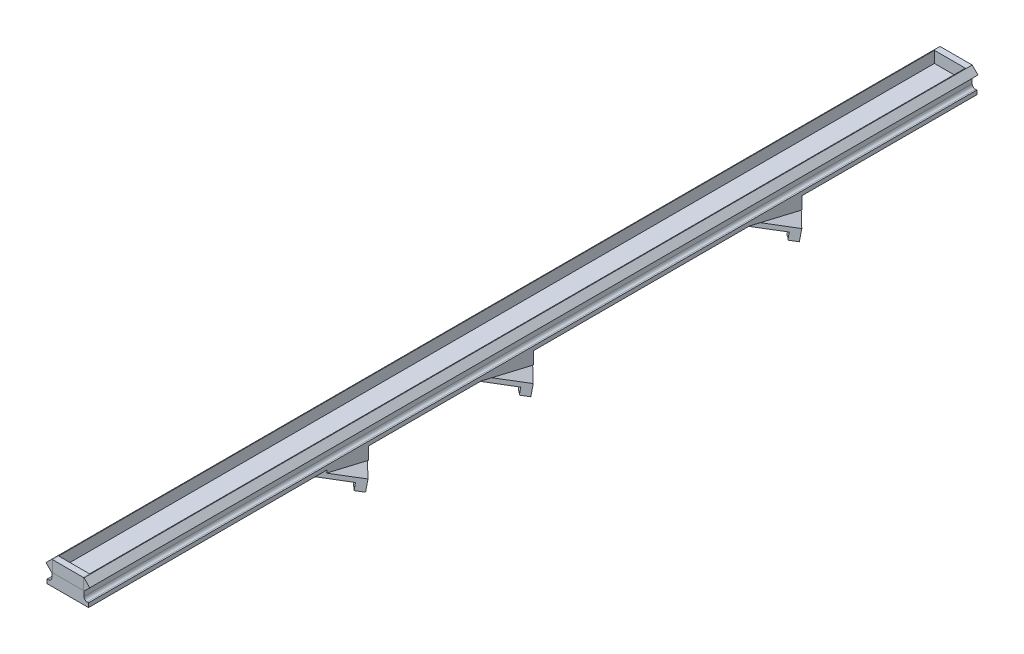
SolidWorks part; units mm, degrees
ref_plane "前视基准面" through (0, 0, 0) normal (0, 0, 1) x (1, 0, 0)
ref_plane "上视基准面" through (0, 0, 0) normal (0, 1, 0) x (1, 0, 0)
ref_plane "右视基准面" through (0, 0, 0) normal (1, 0, 0) x (0, 0, -1)
other "Configuration Table"
sketch "草图1" plane through (0, 0, 0) normal (0, 0, 1) x (1, 0, 0)
  line L0 (0, 0) -> (0, -50000) construction
  line L1 (0, 0) -> (-50000, 0) construction
  line L2 (10, 0) -> (-10, 0)
  line L3 (-10, 0) -> (-10, 2)
  line L4 (-10, 2) -> (-9.3, 2)
  line L5 (-7.8, 3.5) -> (-7.8, 5.8)
  line L6 (-7.8, 5.8) -> (-10.6, 8.6)
  line L7 (-10.6, 8.6) -> (-7.8, 11.4)
  line L8 (-7.8, 11.4) -> (7.8, 11.4)
  line L9 (10.6, 8.6) -> (7.8, 11.4)
  line L10 (7.8, 5.8) -> (10.6, 8.6)
  line L11 (7.8, 3.5) -> (7.8, 5.8)
  line L12 (10, 2) -> (9.3, 2)
  line L13 (10, 0) -> (10, 2)
  arc A0 (-9.3, 2) -> (-7.8, 3.5) centre (-9.3, 3.5) ccw
  arc A1 (9.3, 2) -> (7.8, 3.5) centre (9.3, 3.5) cw
  point P21 (0, 11.4)
  point P25 (0, 0)
  dimension "D7" = 1.5
  dimension "D1" = 45
  dimension "D2" = 21.2
  dimension "D3" = 15.6
  dimension "D4" = 9.4
  dimension "D5" = 2
  dimension "D6" = 20
ref_plane "基准面1" through (0, 0, -150) normal (0, 0, 1) x (1, 0, 0)
sketch "草图2" plane through (0, 0, -150) normal (0, 0, 1) x (1, 0, 0)
  line L0 (-120, 0) -> (-120, -50000) construction
  line L2 (0, 200000) -> (0, -250000) construction
  line L3 (-120, 40) -> (49880, 40) construction
  line L4 (200000, 0) -> (-250000, 0) construction
  point P8 (-120, 40)
  dimension "D1" = 120
  dimension "D2" = 40
sketch3d "3D草图1"
  line L0 (-120, 40, -150) -> (0, 0, 0)
extrude "凸台-拉伸1" add sketch "草图1" along normal blind 230 contours L8 L9 L10 L11 A1 L12 L13 L2 L3 L4 A0 L5 L6 L7
ref_plane "基准面2" through (120, 0, 120) normal (0.7071, 0, 0.7071) x (0, 1, 0)
sketch "草图6" plane through (10, 0, 0) normal (1, 0, 0) x (0, 0, -1)
  line L0 (-210, 0) -> (-184.5388, -6)
  line L1 (-184.5388, -6) -> (-184.5388, 0)
  line L2 (-230, 0) -> (0, 0) construction
  line L3 (-184.5388, 0) -> (-210, 0)
  line L4 (-230, 0) -> (-230, 2) construction
  dimension "D1" = 13.26
  dimension "D2" = 6
  dimension "D3" = 20
extrude "凸台-拉伸4" add sketch "草图6" against normal up to surface (20 mm away) up to face at (-10, 1, 115)
sketch "草图9" plane through (0, -46.8836, 11.0483) normal (0, -0.9733, 0.2294) x (1, 0, 0)
  line L0 (-2.4749, 211.4745) -> (20.1525, 188.8471)
  line L1 (-2.4749, 211.4745) -> (-20.1525, 193.7968)
  line L2 (20.1525, 188.8471) -> (2.4749, 171.1694)
  line L3 (-20.1525, 193.7968) -> (2.4749, 171.1694)
  line L4 (10, 204.4012) -> (10, 178.2427) construction
  line L5 (10, 204.4012) -> (-10, 178.2427) construction
  line L7 (-10, 204.4012) -> (-10, 178.2427) construction
  line L8 (-10, 178.2427) -> (10, 178.2427) construction
  line L9 (-20.1525, 193.7968) -> (20.1525, 188.8471) construction
  point P7 (0, 191.322)
  dimension "D1" = 135
  dimension "D2" = 32
  dimension "D3" = 25
extrude "凸台-拉伸5" add sketch "草图9" along normal blind 7
sketch "草图11" plane through (0, -53.6969, 12.6538) normal (0, -0.9733, 0.2294) x (1, 0, 0)
  line L0 (10.6, 1.9726) -> (10, 1.835)
  line L2 (10.6, 1.9726) -> (10, 1.835)
  line L4 (10, 1.835) -> (10, 0.4587)
  line L6 (10, 1.835) -> (10, 0.4587)
  line L16 (10, 0.4587) -> (10, 0)
  line L20 (10, 0.4587) -> (10, 0)
  line L41 (10, 0) -> (-10, 0)
  line L43 (10, 0) -> (-10, 0)
  line L44 (-10, 0) -> (-10, 0.4587)
  line L45 (-10, 0) -> (-10, 0.4587)
  line L46 (-10, 0.4587) -> (-10, 1.835)
  line L48 (-10, 1.835) -> (-10.6, 1.9726)
  line L49 (-10, 1.835) -> (-10.6, 1.9726)
  line L50 (-10.6, 1.9726) -> (-10.6, 184.2443)
  line L51 (-10.6, 1.9726) -> (-10.6, 184.2443)
  line L52 (-10.6, 184.2443) -> (-20.1525, 193.7968)
  line L53 (-10.6, 184.2443) -> (-20.1525, 193.7968)
  line L54 (-20.1525, 193.7968) -> (-10.6, 203.3494)
  line L55 (-20.1525, 193.7968) -> (-10.6, 203.3494)
  line L56 (-10.6, 203.3494) -> (-10.6, 225.8406)
  line L58 (-10.6, 203.3494) -> (-10.6, 225.8406)
  line L59 (-10.6, 225.8406) -> (-7.8, 226.4828)
  line L60 (-10.6, 225.8406) -> (-7.8, 226.4828)
  line L62 (-7.8, 226.4828) -> (7.8, 226.4828)
  line L63 (-7.8, 226.4828) -> (7.8, 226.4828)
  line L66 (10.6, 198.3996) -> (20.1525, 188.8471)
  line L67 (10.6, 198.3996) -> (20.1525, 188.8471)
  line L70 (7.8, 226.4828) -> (10.6, 225.8406)
  line L71 (7.8, 226.4828) -> (10.6, 225.8406)
  line L72 (10.6, 225.8406) -> (10.6, 198.3996)
  line L73 (10.6, 225.8406) -> (10.6, 198.3996)
  line L76 (20.1525, 188.8471) -> (10.6, 179.2945)
  line L77 (20.1525, 188.8471) -> (10.6, 179.2945)
  line L78 (10.6, 179.2945) -> (10.6, 1.9726)
  line L79 (10.6, 179.2945) -> (10.6, 1.9726)
  line L80 (7.8, 226.4828) -> (-10.6, 203.3494)
  line L81 (20.1525, 188.8471) -> (10.6, 198.3996)
  line L87 (-10, 0.4587) -> (-10, 1.835)
  line M21 (-2.4749, 211.4745) -> (-20.1525, 193.7968)
  line M24 (20.1525, 188.8471) -> (-2.4749, 211.4745)
sketch "草图12" plane through (104.4998, 23.9692, 101.7138) normal (0.7071, 0.1622, 0.6883) x (0.6708, 0.1539, -0.7255)
  line L0 (-144.7463, -6.4402) -> (-15953.1581, -47441.5972) construction
  line L1 (-130.6084, -14.6237) -> (-160.9669, -4.5063) construction
  line L2 (-157.1721, -5.771) -> (-155.5912, -1.0275)
  line L3 (-155.5912, -1.0275) -> (-132.8224, -8.6155)
  line L4 (-157.1721, -5.771) -> (-134.4032, -13.359)
  line L5 (-134.4032, -13.359) -> (-132.8224, -8.6155)
  point P4 (-145.7876, -9.565)
  point P10 (-145.7876, -9.565)
  point P11 (-144.2068, -4.8215)
  dimension "D1" = 24
  dimension "D2" = 5
extrude "切除-拉伸2" cut sketch "草图12" against normal through all
sketch "草图13" plane through (-84.3473, 19.3468, 82.0985) normal (0.7071, -0.1622, -0.6883) x (-0.6708, 0.1539, -0.7255)
  line L0 (-144.7463, -6.4402) -> (-15947.2128, -47423.7574) construction
  line L1 (-133.9289, -13.5171) -> (-157.6464, -5.6129) construction
  line L2 (-132.348, -8.7736) -> (-156.0656, -0.8694) construction
  line L3 (-157.0457, -3.8104) -> (-133.3281, -11.7146)
  line L4 (-157.6464, -5.6129) -> (-155.4333, 1.028) construction
  line L5 (-133.9289, -13.5171) -> (-131.7157, -6.8762) construction
  line L6 (-133.3281, -11.7146) -> (-133.9289, -13.5171)
  line L7 (-133.9289, -13.5171) -> (-157.6464, -5.6129)
  line L8 (-157.6464, -5.6129) -> (-157.0457, -3.8104)
  circle A0 centre (-151.0658, -4.4329) radius 0.8
  circle A1 centre (-138.486, -8.6253) radius 0.8
  circle A2 centre (-151.0658, -4.4329) radius 2.4
  circle A3 centre (-138.486, -8.6253) radius 2.4
  point P4 (-145.7876, -9.565)
  line M4 (-155.4333, 1.028) -> (-157.6464, -5.6129)
  line M5 (-157.6464, -5.6129) -> (-133.9289, -13.5171)
  line M6 (-133.9289, -13.5171) -> (-131.7157, -6.8762)
  dimension "D1" = 13.26
  dimension "D2" = 1.6
  dimension "D3" = 1.8
  dimension "D4" = 4.8
  dimension "D5" = 3.1
extrude "切除-拉伸3" cut sketch "草图13" against normal through all contours L0 L3 A2 M4 M5 | L3 L0 L7 A3 M6 | A0 | A1 region at (9.6829, -11.0667, 185.8713) region at (11.4108, -11.4615, 187.7395) region at (16.0018, -8.2184, 191.6921) region at (6.6256, -10.369, 182.5658)
extrude "切除-拉伸4" cut sketch "草图11" against normal through all contours L73 L71 M24 | L63 L60 L58 M21 region at (5.4499, -4.8212, 220.0593) region at (-4.4446, -3.5245, 225.562)
pattern_linear "阵列(线性)1" count 2 spacing 80 along (0, 0, -1) of "切除-拉伸3", "凸台-拉伸5", "凸台-拉伸4", "切除-拉伸2"
extrude "凸台-拉伸6" add sketch "草图1<3>" against normal blind 110
sketch "草图1<3>" plane through (0, 0, 0) normal (0, 0, 1) x (1, 0, 0) same geometry as "草图1"
extrude "凸台-拉伸7" add sketch "草图1<4>" along normal blind 320
sketch "草图1<4>" plane through (0, 0, 0) normal (0, 0, 1) x (1, 0, 0) same geometry as "草图1"
sketch "草图14" plane through (0, 0, 320) normal (0, 0, 1) x (1, 0, 0)
  line L0 (0, 11.4) -> (0, -49988.6) construction
  line L1 (7.8, 11.4) -> (-7.8, 11.4) construction
  line L3 (-7.5, 5.9) -> (7.5, 5.9)
  line L4 (-7.5, 5.9) -> (-7.5, 11.4)
  line L5 (-7.5, 11.4) -> (7.5, 11.4)
  line L6 (7.5, 5.9) -> (7.5, 11.4)
  line L7 (-7.5, 5.9) -> (7.5, 11.4) construction
  line L8 (-7.5, 11.4) -> (7.5, 5.9) construction
  point P4 (0, 11.4)
  point P5 (0, 8.65)
  dimension "D1" = 5.5
  dimension "D2" = 15
extrude "切除-拉伸5" cut sketch "草图14" against normal through all
sketch "草图15" plane through (0, 0, -110) normal (0, 0, -1) x (-1, 0, 0)
  line L1 (-7.5, 5.9) -> (7.5, 5.9)
  line L2 (-7.5, 5.9) -> (-7.5, 11.4)
  line L3 (-7.5, 11.4) -> (7.5, 11.4)
  line L4 (7.5, 5.9) -> (7.5, 11.4)
extrude "凸台-拉伸8" add sketch "草图15" against normal blind 3
sketch "草图16" plane through (0, 0, 320) normal (0, 0, 1) x (1, 0, 0)
  line L1 (-7.5, 5.9) -> (7.5, 5.9)
  line L2 (-7.5, 5.9) -> (-7.5, 11.4)
  line L3 (-7.5, 11.4) -> (7.5, 11.4)
  line L4 (7.5, 5.9) -> (7.5, 11.4)
extrude "凸台-拉伸9" add sketch "草图16" against normal blind 3 separate body
pattern_linear "阵列(线性)2" count 2 spacing 210 along (0, 0, -1) of "凸台-拉伸4", "凸台-拉伸5", "切除-拉伸2", "切除-拉伸3"
